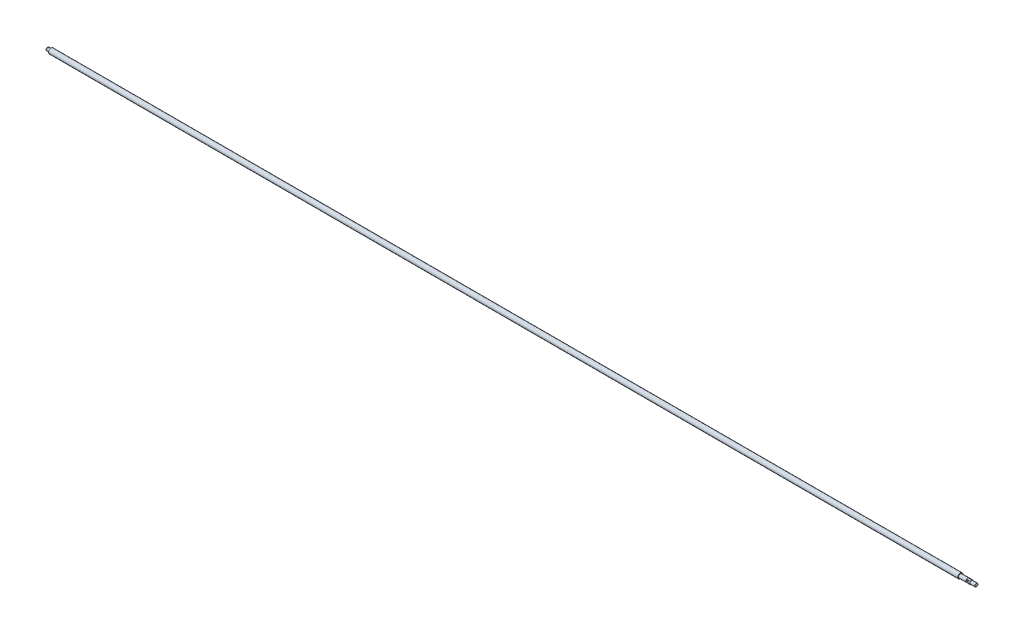
SolidWorks part; units mm, degrees
material "Хромистая нержавеющая сталь"
ref_plane "Спереди" through (0, 0, 0) normal (0, 0, 1) x (1, 0, 0)
ref_plane "Сверху" through (0, 0, 0) normal (0, 1, 0) x (1, 0, 0)
ref_plane "Справа" through (0, 0, 0) normal (1, 0, 0) x (0, 0, -1)
sketch "Эскиз1" plane through (0, 0, 0) normal (0, 0, 1) x (1, 0, 0)
  line L0 (-2810.0019, 5.9419) -> (-2810.0019, 10.8919)
  line L1 (-2810.0019, 10.8919) -> (-2808.0519, 10.8919)
  line L2 (-2808.0519, 10.8919) -> (-2808.0519, 10.7419)
  line L3 (-2808.0519, 10.7419) -> (-2806.9019, 10.7419)
  line L4 (-2806.9019, 10.7419) -> (-2806.9019, 10.9419)
  line L5 (-2806.9019, 10.9419) -> (-2799.0019, 10.9419)
  line L6 (-2799.0019, 10.9419) -> (-2799.0019, 13.9419)
  line L7 (-2799.0019, 13.9419) -> (39.9981, 13.9419)
  line L8 (39.9981, 13.9419) -> (39.9981, 11.9419)
  line L9 (39.9981, 11.9419) -> (74.9981, 11.9419)
  line L10 (74.9981, 11.9419) -> (74.9981, 10.8919)
  line L11 (74.9981, 10.8919) -> (89.9981, 10.8919)
  line L12 (89.9981, 10.8919) -> (89.9981, 5.9419)
  line L13 (89.9981, 5.9419) -> (-2810.0019, 5.9419)
  line L14 (60.9981, 14.6846) -> (60.9981, -1.3142) construction
  dimension "D1" = 1.15
  dimension "D2" = 7.9
  dimension "D3" = 11
  dimension "D4" = 35
  dimension "D5" = 50
  dimension "D6" = 14
  dimension "D7" = 4.95
  dimension "D8" = 1.05
  dimension "D9" = 2
  dimension "D10" = 4.95
  dimension "D11" = 4.8
  dimension "D12" = 5
  dimension "D13" = 2900
revolve "Повернуть1" add sketch "Эскиз1" angle 360 about L13
ref_plane "Плоскость1" through (49.9981, 0, 0) normal (1, 0, 0) x (0, 0, -1)
sketch "Эскиз2" plane through (49.9981, 0, 0) normal (1, 0, 0) x (0, 0, -1)
  circle A0 centre (0, 5.9419) radius 8 construction
  circle A1 centre (0, 5.9419) radius 8
curve "Спираль1" pitch 5 height 290 turns 58
sketch "Эскиз3" plane through (0, 0, 0) normal (0, 0, 1) x (1, 0, 0)
  line L0 (-207.8405, -2.5666) -> (-201.4949, -2.5666) construction
  line L1 (-210.2778, -2.0666) -> (-203.5838, -2.0666) construction
  line L2 (-207.8405, -4.8575) -> (-207.8405, -1.8666) construction
  line L3 (-205.3405, -4.8575) -> (-205.3405, -0.2923) construction
  line L4 (-205.3405, -1.8666) -> (-205.4905, -2.0666)
  line L5 (-205.4905, -2.0666) -> (-205.4905, -2.5666)
  line L6 (-205.4905, -2.5666) -> (-205.1905, -2.5666)
  line L7 (-205.1905, -2.5666) -> (-205.1905, -2.0666)
  line L8 (-205.1905, -2.0666) -> (-205.3405, -1.8666)
  circle A0 centre (-207.8405, -2.5666) radius 1.5875
  point P7 (-207.7498, -2.0666)
  dimension "D1" = 3.175
  dimension "D2" = 0.5
  dimension "D3" = 2.5
  dimension "D4" = 0.2
  dimension "D5" = 0.3
ref_plane "Плоскость2" through (84.9981, 0, 0) normal (1, 0, 0) x (0, 0, -1)
sketch "Эскиз4" plane through (84.9981, 0, 0) normal (1, 0, 0) x (0, 0, -1)
  circle A0 centre (0, 5.9419) radius 6 construction
  circle A1 centre (0, 5.9419) radius 6
curve "Спираль2" pitch 1 height 22 radius 6 centre (84.9981, 5.9419, 0) axis (-1, 0, 0) start towards (0, 0, 1)
sketch "Эскиз5" plane through (0, 0, 0) normal (0, 0, 1) x (1, 0, 0)
  line L0 (76.2561, 0.4419) -> (75.7561, -0.0581)
  line L1 (39.9981, -0.0581) -> (74.9981, -0.0581) construction
  line L2 (75.7561, -0.0581) -> (75.7561, -1.0581)
  line L3 (75.7561, -1.0581) -> (76.7561, -1.0581)
  line L4 (76.7561, -1.0581) -> (76.7561, -0.0581)
  line L5 (76.7561, -0.0581) -> (76.2561, 0.4419)
  line L6 (76.2561, 0.4419) -> (76.2561, -0.2584) construction
  line L7 (75.7561, -0.0581) -> (76.7561, -0.0581) construction
  dimension "D1" = 0.5
  dimension "D2" = 1
  dimension "D3" = 1
sweep "Вырез-По траектории7" cut profiles "Эскиз5" path "Спираль2" align with end faces yes
